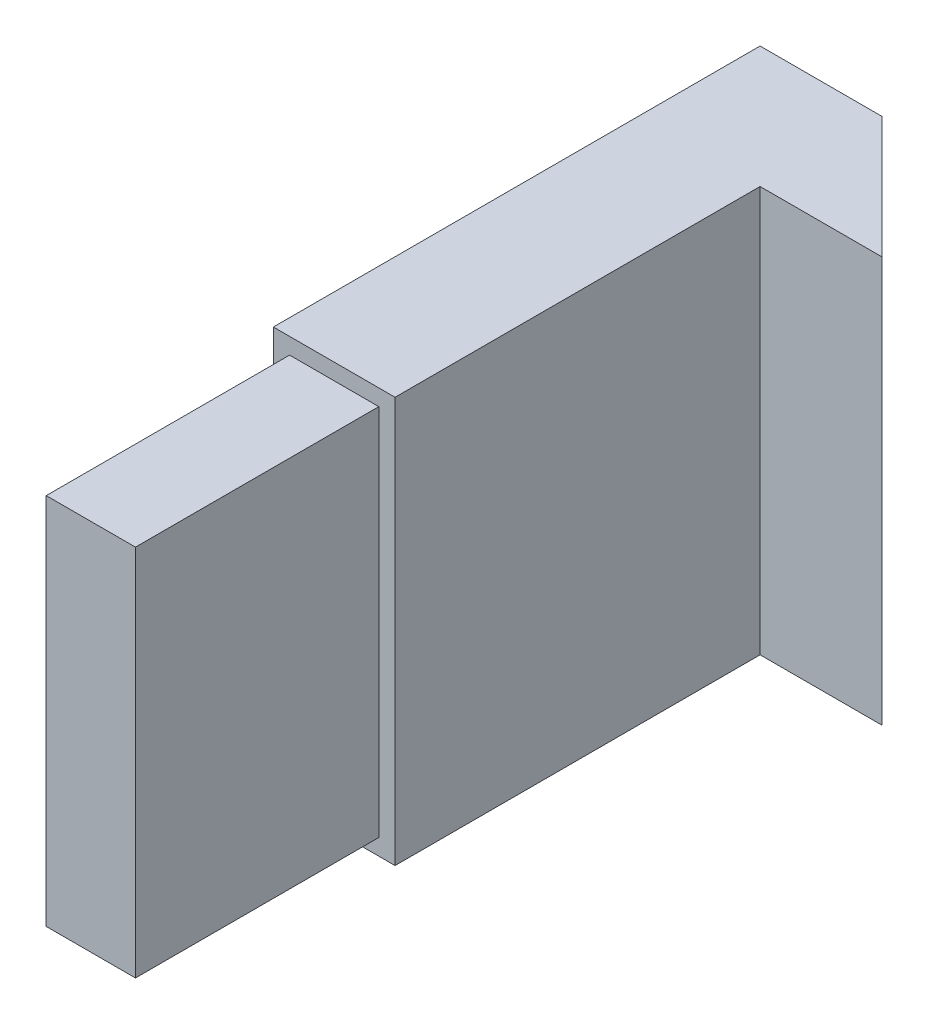
SolidWorks part; units mm, degrees
ref_plane "Front Plane" through (0, 0, 0) normal (0, 0, 1) x (1, 0, 0)
ref_plane "Top Plane" through (0, 0, 0) normal (0, 1, 0) x (1, 0, 0)
ref_plane "Right Plane" through (0, 0, 0) normal (1, 0, 0) x (0, 0, -1)
sketch "Sketch1" plane through (0, 0, 0) normal (0, 1, 0) x (1, 0, 0)
  line L0 (2.25, 1.5) -> (0.75, 3)
  line L1 (-0.75, -3) -> (0.75, -3)
  line L5 (-0.7, -3) -> (0.7, -3)
  line L7 (-0.75, 3) -> (0.75, 3)
  line L8 (-0.75, 3) -> (-0.75, -3)
  line L9 (-0.75, -3) -> (0.75, -3)
  line L10 (0.75, 1.5) -> (0.75, -3)
  line L11 (-0.75, 3) -> (0.75, -3) construction
  line L12 (-0.75, -3) -> (0.75, 3) construction
  line L13 (0.75, 1.5) -> (0.75, 3) construction
  line L15 (0.75, 1.5) -> (2.25, 1.5)
  point P6 (0, 0)
  dimension "D1" = 1.5
  dimension "D3" = 6
extrude "Boss-Extrude1" add sketch "Sketch1" along normal blind 5 contours L1 | L10 L15 L0 L7 L8 L1 region at (0.1389, 0, -0.2222)
sketch "Sketch2" plane through (0, 0, 3) normal (0, 0, 1) x (1, 0, 0)
  line L8 (-0.55, 0.2) -> (0.55, 0.2)
  line L9 (0.55, 0.2) -> (0.55, 4.8)
  line L10 (0.55, 4.8) -> (-0.55, 4.8)
  line L11 (-0.55, 4.8) -> (-0.55, 0.2)
  line L12 (-0.55, 0.2) -> (0.55, 0.2)
  line L13 (0.55, 0.2) -> (0.55, 4.8)
  line L14 (0.55, 4.8) -> (-0.55, 4.8)
  line L15 (-0.55, 4.8) -> (-0.55, 0.2)
  dimension "D1" = 0.2
extrude "Boss-Extrude2" add sketch "Sketch2" along normal blind 3
